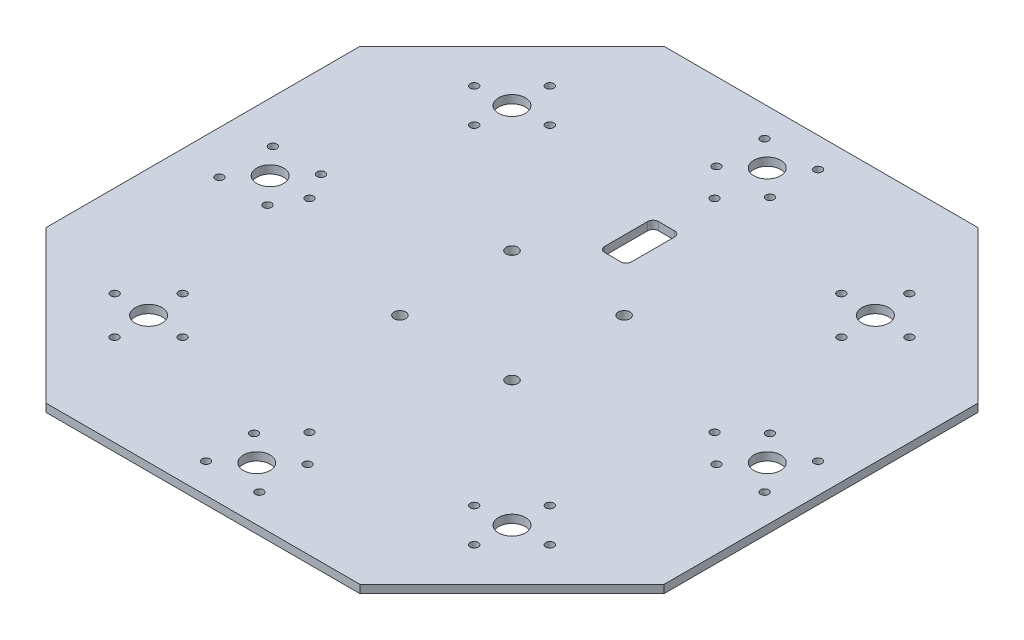
SolidWorks part; units mm, degrees
ref_plane "Front Plane" through (0, 0, 0) normal (0, 0, 1) x (1, 0, 0)
ref_plane "Top Plane" through (0, 0, 0) normal (0, 1, 0) x (1, 0, 0)
ref_plane "Right Plane" through (0, 0, 0) normal (1, 0, 0) x (0, 0, -1)
sketch "Sketch1" plane through (0, 0, 0) normal (0, 1, 0) x (1, 0, 0)
  line L1 (0, 0) -> (230, 0)
  line L2 (0, 0) -> (0, 230)
  line L3 (0, 230) -> (230, 230)
  line L4 (230, 0) -> (230, 230)
  dimension "D1" = 230
  dimension "D2" = 230
extrude "Boss-Extrude1" add sketch "Sketch1" along normal blind 3
fillet "Chamfer2" radius 56.5685 1 edges at (0, 1.5, 0) type face fillet profile chamfer first side face at (115, 1.5, 0) second side face at (0, 1.5, -115)
fillet "Chamfer3" radius 56.5685 1 edges at (0, 1.5, -230) type face fillet profile chamfer first side face at (0, 1.5, -143.2843) second side face at (115, 1.5, -230)
fillet "Chamfer4" radius 56.5685 1 edges at (230, 1.5, -230) type face fillet profile chamfer first side face at (143.2842, 1.5, -230) second side face at (230, 1.5, -115)
fillet "Chamfer5" radius 56.5685 1 edges at (230, 1.5, 0) type face fillet profile chamfer first side face at (230, 1.5, -86.7158) second side face at (143.2843, 1.5, 0)
hole_wizard "11/64 (0.17188) Diameter Hole1" positions "Sketch4" profile "Sketch3" hole size "11/64" standard "ANSI Inch" end condition up to next
sketch "Sketch4" plane through (0, 3, 0) normal (0, 1, 0) x (1, 0, 0)
  point P0 (94.1403, 135.8597)
  point P3 (135.8597, 135.8597)
  point P6 (135.8597, 94.1403)
  point P9 (94.1403, 94.1403)
sketch "Sketch3" plane through (94.1403, 3, -135.8597) normal (1, 0, 0) x (0, 0, 1)
  line L0 (0, 0) -> (0, 3)
  line L1 (0, 3) -> (2.1829, 3)
  line L2 (2.1829, 3) -> (2.1829, 0)
  line L5 (2.1829, 0) -> (0, 0)
  line L11 (0, -6.35) -> (0, 107.95) construction
  dimension "Thru Hole Dia." = 4.3658
  dimension "Thru Hole Depth" = 3
sketch "Sketch11" plane through (0, 3, 0) normal (0, 1, 0) x (1, 0, 0)
  line L0 (230, 115) -> (0, 115) construction
  line L1 (230, 56.5685) -> (230, 173.4315) construction
  line L2 (0, 173.4315) -> (0, 56.5685) construction
  line L4 (115, 115) -> (115, 152.5) construction
  line L5 (115, 152.5) -> (120, 152.5)
  line L6 (115, 152.5) -> (110, 152.5)
  line L7 (120, 152.5) -> (120, 172.5)
  line L8 (120, 172.5) -> (110, 172.5)
  line L9 (110, 152.5) -> (110, 172.5)
extrude "Cut-Extrude3" cut sketch "Sketch11" against normal through all
fillet "Fillet9" radius 2 1 edges at (120, 1.5, -172.5) type face fillet first side face at (120, 1.5, -162.5) second side face at (115, 1.5, -172.5)
fillet "Fillet10" radius 2 1 edges at (110, 1.5, -172.5) type face fillet first side face at (114, 1.5, -172.5) second side face at (110, 1.5, -162.5)
fillet "Fillet11" radius 2 1 edges at (120, 1.5, -152.5) type face fillet first side face at (120, 1.5, -161.5) second side face at (115, 1.5, -152.5)
fillet "Fillet12" radius 2 1 edges at (110, 1.5, -152.5) type face fillet first side face at (114, 1.5, -152.5) second side face at (110, 1.5, -161.5)
hole_wizard "Ø10.0mm Dowel Hole1" positions "Sketch12" profile "Sketch13" hole size "Ø10.0" standard "ANSI Metric" end condition up to next
sketch "Sketch12" plane through (0, 3, 0) normal (0, 1, 0) x (1, 0, 0)
  point P0 (210, 115)
  point P3 (182.6239, 182.6239)
  point P6 (182.6239, 47.3761)
  point P9 (115, 20)
  point P12 (47.3761, 47.3761)
  point P15 (25, 115)
  point P18 (47.3761, 182.6239)
  point P21 (115, 210)
  point P25 (0, 0)
  point P26 (0, 0)
  point P27 (0, 0)
  point P28 (0, 0)
  point P29 (0, 0)
  point P30 (0, 0)
  point P31 (0, 0)
  point P32 (0, 0)
  point P33 (0, 0)
sketch "Sketch13" plane through (210, 3, -115) normal (1, 0, 0) x (0, 0, 1)
  line L0 (0, 0) -> (0, 3)
  line L1 (0, 3) -> (5, 3)
  line L2 (5, 3) -> (5, 0)
  line L5 (5, 0) -> (0, 0)
  line L11 (0, -6.35) -> (0, 107.95) construction
  dimension "Thru Hole Dia." = 10
  dimension "Thru Hole Depth" = 3
hole_wizard "Ø3.0mm Dowel Hole1" positions "Sketch16" profile "Sketch15" hole size "Ø3.0" standard "ANSI Metric" end condition up to next
sketch "Sketch16" plane through (0, 0, 0) normal (0, -1, 0) x (-1, 0, 0)
  point P0 (-201.05, 124.95)
  point P3 (-201.05, 105.05)
  point P6 (-218.95, 124.95)
  point P9 (-218.95, 105.05)
  point P12 (-183.331, 60.7405)
  point P15 (-169.2595, 46.669)
  point P18 (-181.9168, 34.0118)
  point P21 (-195.9882, 48.0832)
  point P24 (-183.331, 169.2595)
  point P27 (-169.2595, 183.331)
  point P30 (-181.9168, 195.9882)
  point P33 (-195.9882, 181.9168)
  point P36 (-124.95, 201.05)
  point P39 (-124.95, 218.95)
  point P42 (-105.05, 218.95)
  point P45 (-105.05, 201.05)
  point P48 (-60.7405, 183.331)
  point P51 (-34.0118, 181.9168)
  point P54 (-46.669, 169.2595)
  point P57 (-48.0832, 195.9882)
  point P60 (-16.05, 124.95)
  point P63 (-33.95, 105.05)
  point P66 (-33.95, 124.95)
  point P69 (-16.05, 105.05)
  point P72 (-60.7405, 46.669)
  point P75 (-48.0832, 34.0118)
  point P78 (-46.669, 60.7405)
  point P81 (-34.0118, 48.0832)
  point P84 (-105.05, 28.95)
  point P87 (-105.05, 11.05)
  point P90 (-124.95, 28.95)
  point P93 (-124.95, 11.05)
  point P97 (0, 0)
  point P98 (0, 0)
  point P99 (0, 0)
  point P100 (0, 0)
  point P101 (0, 0)
  point P102 (0, 0)
  point P103 (0, 0)
  point P104 (0, 0)
  point P105 (0, 0)
  point P106 (0, 0)
  point P107 (0, 0)
  point P108 (0, 0)
  point P109 (0, 0)
  point P110 (0, 0)
  point P111 (0, 0)
  point P112 (0, 0)
  point P113 (0, 0)
  point P114 (0, 0)
  point P115 (0, 0)
  point P116 (0, 0)
  point P117 (0, 0)
  point P118 (0, 0)
  point P119 (0, 0)
  point P120 (0, 0)
  point P121 (0, 0)
  point P122 (0, 0)
  point P123 (0, 0)
  point P124 (0, 0)
  point P125 (0, 0)
  point P126 (0, 0)
  point P127 (0, 0)
  point P128 (0, 0)
sketch "Sketch15" plane through (201.05, 0, -124.95) normal (1, 0, 0) x (0, 0, -1)
  line L0 (0, 0) -> (0, 3)
  line L1 (0, 3) -> (1.5, 3)
  line L2 (1.5, 3) -> (1.5, 0)
  line L5 (1.5, 0) -> (0, 0)
  line L11 (0, -6.35) -> (0, 107.95) construction
  dimension "Thru Hole Dia." = 3
  dimension "Thru Hole Depth" = 3
hole_wizard "Ø3.0mm Dowel Hole2" positions "Sketch17" profile "Sketch18" hole size "Ø3.0" standard "ANSI Metric" end condition up to next
sketch "Sketch17" plane through (0, 3, 0) normal (0, 1, 0) x (1, 0, 0)
  point P0 (115, 190.375)
  point P3 (39.625, 115)
  point P6 (115, 39.625)
  point P9 (190.375, 115)
  point P13 (0, 0)
  point P14 (0, 0)
  point P15 (0, 0)
  point P16 (0, 0)
sketch "Sketch18" plane through (115, 3, -190.375) normal (1, 0, 0) x (0, 0, 1)
  line L0 (0, 0) -> (0, 3)
  line L1 (0, 3) -> (1.5, 3)
  line L2 (1.5, 3) -> (1.5, 0)
  line L5 (1.5, 0) -> (0, 0)
  line L11 (0, -6.35) -> (0, 107.95) construction
  dimension "Thru Hole Dia." = 3
  dimension "Thru Hole Depth" = 3
